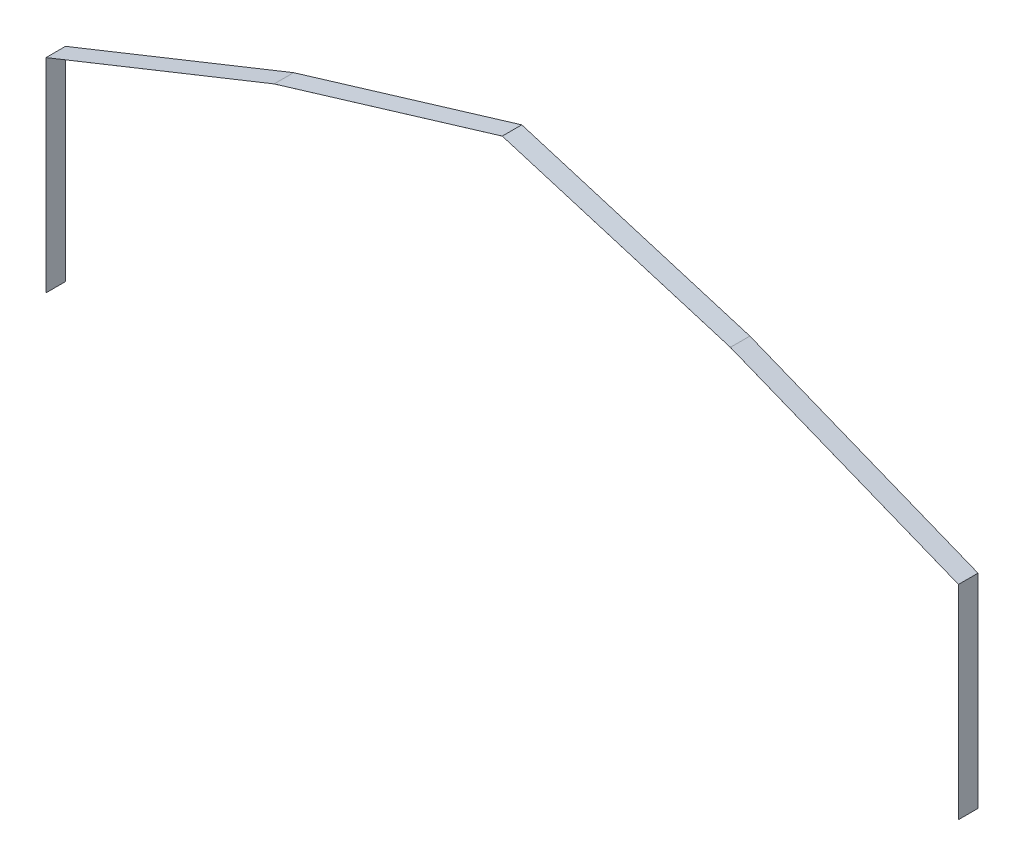
SolidWorks part; units mm, degrees
ref_plane "Alzado" through (0, 0, 0) normal (0, 0, 1) x (1, 0, 0)
ref_plane "Planta" through (0, 0, 0) normal (0, 1, 0) x (1, 0, 0)
ref_plane "Vista lateral" through (0, 0, 0) normal (1, 0, 0) x (0, 0, -1)
sketch "Croquis1" plane through (0, 0, 0) normal (0, 0, 1) x (1, 0, 0)
  line L0 (0, 0) -> (5943.6, 2377.44)
  line L1 (5943.6, 2377.44) -> (11887.2, 4172.0782)
  line L2 (0, 0) -> (11887.2, 0) construction
  line L3 (11887.2, 0) -> (11887.2, 4172.0782) construction
  line L4 (5943.6, 2377.44) -> (5943.6, 0) construction
  line L5 (5943.6, 2377.44) -> (11887.2, 4754.88) construction
  line L6 (11887.2, 4172.0782) -> (11887.2, 4754.88) construction
  line L7 (17830.8, 2377.44) -> (11887.2, 4172.0782)
  line L8 (23774.4, 0) -> (17830.8, 2377.44)
  line L9 (0, 0) -> (0, -5308.6)
  line L10 (23774.4, 0) -> (23774.4, -5308.6)
  dimension "D1" = 2377.44
  dimension "D2" = 5943.6
  dimension "D3" = 5
  dimension "D4" = 11887.2
  dimension "D5" = 23774.4
  dimension "D6" = 4172.0782
  dimension "D7" = 5308.6
extrude "Extruir-Lámina1" add sketch "Croquis1" along normal mid plane 508 thin thin type one direction wall 0.254
